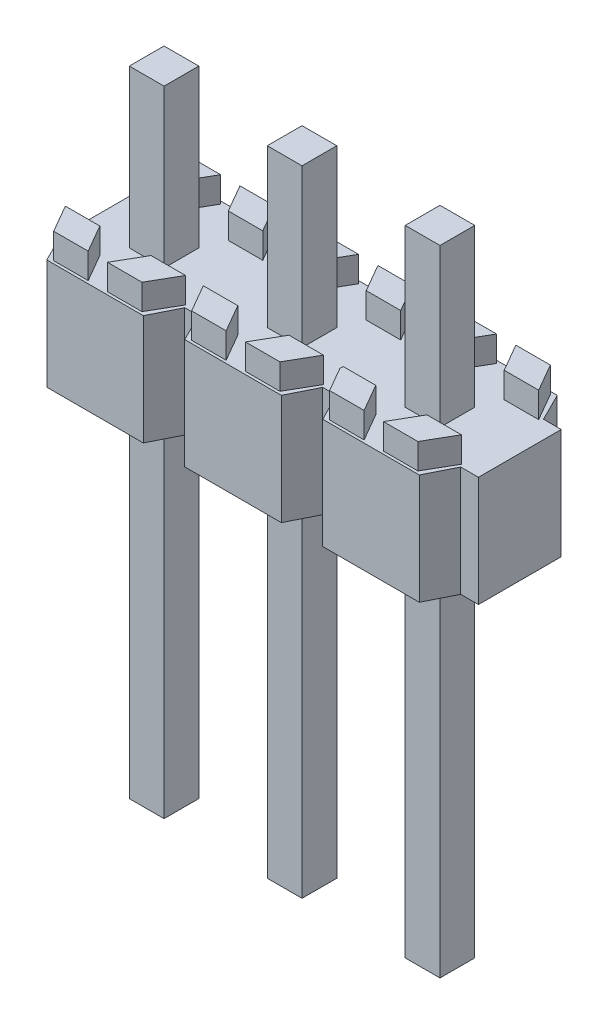
SolidWorks part; units mm, degrees
ref_plane "Front Plane" through (0, 0, 0) normal (0, 0, 1) x (1, 0, 0)
ref_plane "Top Plane" through (0, 0, 0) normal (0, 1, 0) x (1, 0, 0)
ref_plane "Right Plane" through (0, 0, 0) normal (1, 0, 0) x (0, 0, -1)
sketch "Sketch1" plane through (0, 0, 0) normal (0, 1, 0) x (1, 0, 0)
  line L0 (0, 1.5791) -> (0, -1.5527) construction
  line L2 (-0.32, 0.32) -> (0.32, 0.32)
  line L3 (-0.32, 0.32) -> (-0.32, -0.32)
  line L4 (-0.32, -0.32) -> (0.32, -0.32)
  line L5 (0.32, 0.32) -> (0.32, -0.32)
  line L6 (-0.32, 0.32) -> (0.32, -0.32) construction
  line L7 (-0.32, -0.32) -> (0.32, 0.32) construction
  line L8 (-1.143, 0.762) -> (-0.889, 1.27)
  line L9 (-0.889, 1.27) -> (0.889, 1.27)
  line L10 (0.889, 1.27) -> (1.143, 0.762)
  line L11 (1.143, 0.762) -> (1.47, 0.762)
  line L12 (1.47, 0.762) -> (1.47, -0.762)
  line L13 (1.47, -0.762) -> (1.143, -0.762)
  line L14 (1.143, -0.762) -> (0.889, -1.27)
  line L15 (0.889, -1.27) -> (-0.889, -1.27)
  line L16 (-0.889, -1.27) -> (-1.143, -0.762)
  line L17 (-1.143, -0.762) -> (-1.143, 0.762)
  line L18 (-1.7519, 0.762) -> (1.5375, 0.762) construction
  line L19 (1.0554, 0) -> (-1.5628, 0) construction
  line L20 (-1.697, -0.762) -> (2.4529, -0.762) construction
  point P3 (0, 0)
  dimension "D1" = 0.64
  dimension "D2" = 0.64
  dimension "D3" = 0.889
  dimension "D4" = 1.778
  dimension "D5" = 1.27
  dimension "D6" = 1.143
  dimension "D7" = 0.762
  dimension "D8" = 1.47
extrude "Boss-Extrude1" add sketch "Sketch1" along normal blind 1.48 and the other way blind 1.02
sketch "Sketch2" plane through (0, 1.48, 0) normal (0, 1, 0) x (1, 0, 0)
  line L0 (-1.1061, -0.7112) -> (-0.4711, -0.7112)
  line L1 (-0.4711, -0.7112) -> (-0.1778, -1.2192)
  line L2 (-0.1778, -1.2192) -> (-0.8128, -1.2192)
  line L3 (-1.143, 0.762) -> (-1.143, -0.762) construction
  line L4 (-0.889, 1.27) -> (-1.143, 0.762) construction
  line L5 (-0.8128, -1.2192) -> (-1.1061, -0.7112)
  line L6 (0, 1.3694) -> (0, -1.4569) construction
  line L7 (-1.5186, 0) -> (1.896, 0) construction
  line L8 (-0.8128, 1.2192) -> (-1.1061, 0.7112)
  line L9 (-0.1778, 1.2192) -> (-0.8128, 1.2192)
  line L10 (-0.4711, 0.7112) -> (-0.1778, 1.2192)
  line L11 (-1.1061, 0.7112) -> (-0.4711, 0.7112)
  line L12 (1.1061, 0.7112) -> (0.4711, 0.7112)
  line L13 (0.4711, 0.7112) -> (0.1778, 1.2192)
  line L14 (0.1778, 1.2192) -> (0.8128, 1.2192)
  line L15 (0.8128, 1.2192) -> (1.1061, 0.7112)
  line L16 (0.8128, -1.2192) -> (1.1061, -0.7112)
  line L17 (0.1778, -1.2192) -> (0.8128, -1.2192)
  line L18 (0.4711, -0.7112) -> (0.1778, -1.2192)
  line L19 (1.1061, -0.7112) -> (0.4711, -0.7112)
  line L20 (0.889, 1.27) -> (-0.889, 1.27) construction
  line L21 (1.143, 0.762) -> (0.889, 1.27) construction
  line L22 (1.47, 0.762) -> (1.143, 0.762) construction
  line L23 (1.47, -0.762) -> (1.47, 0.762) construction
  line L24 (1.143, -0.762) -> (1.47, -0.762) construction
  line L25 (0.889, -1.27) -> (1.143, -0.762) construction
  line L26 (-0.889, -1.27) -> (0.889, -1.27) construction
  line L27 (-1.143, -0.762) -> (-0.889, -1.27) construction
  line L28 (-1.143, 0.762) -> (-1.143, -0.762)
  line L29 (-0.889, 1.27) -> (-1.143, 0.762)
  line L30 (0.889, 1.27) -> (-0.889, 1.27)
  line L31 (1.143, 0.762) -> (0.889, 1.27)
  line L32 (1.47, 0.762) -> (1.143, 0.762)
  line L33 (1.47, -0.762) -> (1.47, 0.762)
  line L34 (1.143, -0.762) -> (1.47, -0.762)
  line L35 (0.889, -1.27) -> (1.143, -0.762)
  line L36 (-0.889, -1.27) -> (0.889, -1.27)
  line L37 (-1.143, -0.762) -> (-0.889, -1.27)
extrude "Cut-Extrude2" cut sketch "Sketch2" against normal blind 0.47
sketch "Sketch3" plane through (0, 1.01, 0) normal (0, 1, 0) x (1, 0, 0)
  line L4 (-0.32, 0.32) -> (0.32, 0.32)
  line L5 (0.32, 0.32) -> (0.32, -0.32)
  line L6 (0.32, -0.32) -> (-0.32, -0.32)
  line L7 (-0.32, -0.32) -> (-0.32, 0.32)
extrude "Boss-Extrude2" add sketch "Sketch3" along normal blind 2.9 separate body
sketch "Sketch4" plane through (0, -1.02, 0) normal (0, -1, 0) x (1, 0, 0)
  line L4 (-0.32, -0.32) -> (0.32, -0.32)
  line L5 (0.32, -0.32) -> (0.32, 0.32)
  line L6 (0.32, 0.32) -> (-0.32, 0.32)
  line L7 (-0.32, 0.32) -> (-0.32, -0.32)
  line L8 (-0.32, -0.32) -> (0.32, -0.32)
  line L9 (0.32, -0.32) -> (0.32, 0.32)
  line L10 (0.32, 0.32) -> (-0.32, 0.32)
  line L11 (-0.32, 0.32) -> (-0.32, -0.32)
  dimension "D1" = 0
extrude "Boss-Extrude3" add sketch "Sketch4" along normal blind 6.75 separate body
pattern_linear "LPattern1" count 3 spacing 2.54 along (1, 0, 0) of "Boss-Extrude1", "Cut-Extrude2", "Boss-Extrude2", "Boss-Extrude3"
